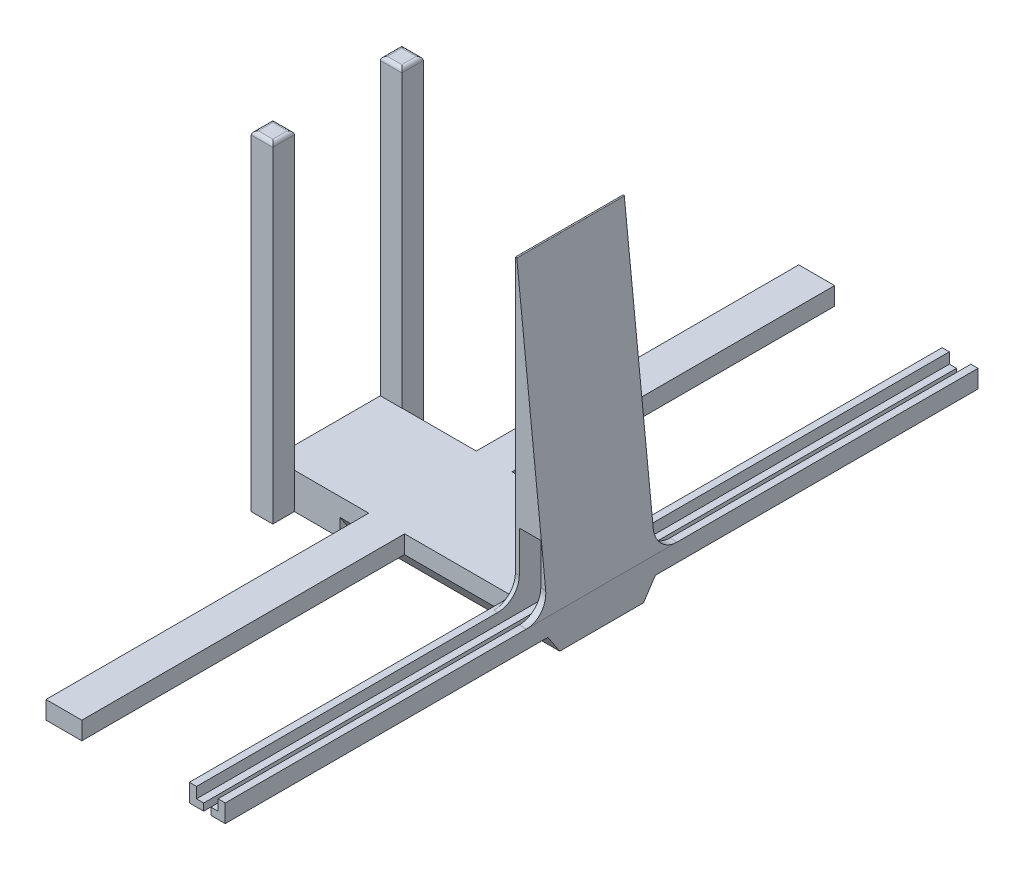
SolidWorks part; units mm, degrees
ref_plane "Front Plane" through (0, 0, 0) normal (0, 0, 1) x (1, 0, 0)
ref_plane "Top Plane" through (0, 0, 0) normal (0, 1, 0) x (1, 0, 0)
ref_plane "Right Plane" through (0, 0, 0) normal (1, 0, 0) x (0, 0, -1)
sketch "Sketch1" plane through (0, -9.4965, 0) normal (0, 1, 0) x (1, 0, 0)
  line L0 (175.5493, -129.0166) -> (125.5493, -129.0166) construction
  line L1 (180.0974, -84.0166) -> (175.0974, -84.0166)
  line L2 (180.0974, -84.0166) -> (180.0974, -189.0166)
  line L3 (180.0974, -189.0166) -> (175.0974, -189.0166)
  line L4 (175.0974, -84.0166) -> (175.0974, -189.0166)
  line L5 (175.5493, -144.0166) -> (125.5493, -144.0166) construction
  dimension "D1" = 60
  dimension "D2" = 60
  dimension "D3" = 5
extrude "Boss-Extrude1" add sketch "Sketch1" along normal blind 5
sketch "Sketch2" plane through (0, -9.4965, 0) normal (0, 0, 1) x (1, 0, 0)
  line L0 (180.0974, 5) -> (175.5493, 48.02)
  line L1 (175.5493, 48.02) -> (175.5493, 5)
  line L2 (180.0974, 5) -> (175.0974, 5) construction
  line L3 (175.5493, 41.5165) -> (175.5493, 56.5165) construction
  line L4 (175.5493, 5) -> (180.0974, 5)
extrude "Boss-Extrude2" add sketch "Sketch2" along normal blind 15 from offset 129
sketch "Sketch3" plane through (0, -9.4965, 0) normal (0, 0, 1) x (1, 0, 0)
  line L1 (175.0974, 5) -> (141.726, 5)
  line L2 (175.0974, 5) -> (175.0974, 0)
  line L3 (175.0974, 0) -> (141.726, 0)
  line L4 (141.726, 5) -> (141.726, 0)
extrude "Boss-Extrude3" add sketch "Sketch3" along normal blind 15 from offset 129
sketch "Sketch4" plane through (0, -9.4965, 0) normal (0, 1, 0) x (1, 0, 0)
  line L0 (175.5493, -144.0166) -> (125.5493, -144.0166) construction
  line L1 (144.726, -147.0166) -> (141.726, -147.0166)
  line L2 (144.726, -147.0166) -> (144.726, -144)
  line L3 (144.726, -144) -> (141.726, -144)
  line L4 (141.726, -147.0166) -> (141.726, -144)
  line L5 (175.5493, -129.0166) -> (125.5493, -129.0166) construction
  line L6 (144.726, -129.0166) -> (141.726, -129.0166)
  line L7 (144.726, -129.0166) -> (144.726, -126.0166)
  line L8 (144.726, -126.0166) -> (141.726, -126.0166)
  line L9 (141.726, -129.0166) -> (141.726, -126.0166)
  dimension "D1" = 3
  dimension "D2" = 3
  dimension "D3" = 3
  dimension "D4" = 3
extrude "Boss-Extrude4" add sketch "Sketch4" along normal blind 46
sketch "Sketch5" plane through (0, 0, 126.0166) normal (0, 0, -1) x (-1, 0, 0)
  circle A0 centre (-143.2664, 42.1424) radius 0.7
fillet "Fillet1" radius 0.5 8 edges at (143.226, 36.5035, 129.0166) (141.726, 36.5035, 127.5166) (143.226, 36.5035, 126.0166) (144.726, 36.5035, 127.5166) (143.226, 36.5035, 147.0166) (141.726, 36.5035, 145.5083) (143.226, 36.5035, 144) (144.726, 36.5035, 145.5083)
fillet "Fillet2" radius 0.1 1 edges at (175.5493, 38.5235, 136.5)
sketch "Sketch6" plane through (177.6366, 18.7798, 0) normal (0.9945, 0.1051, 0) x (0, 0, -1)
  line L0 (-144, -23.4061) -> (-144, 17.9566) construction
  line L1 (-129, -23.4061) -> (-129, 17.9566) construction
  circle A0 centre (-141.5, 22.489) radius 0.7
  circle A1 centre (-131.5, 22.489) radius 0.7
  dimension "D1" = 2.5
  dimension "D2" = 2.5
ref_plane "Plane1" through (180.0974, -4.4965, 144) normal (1, 0, 0) x (0, 0, -1)
fillet "Fillet3" radius 3 2 edges at (177.8233, -4.4965, 129) (177.8233, -4.4965, 144)
pattern_linear "LPattern2" count 2 spacing 20 along (-1, 0, 0) of "Boss-Extrude1"
sketch "Sketch7" plane through (180.0974, 0, 0) normal (1, 0, 0) x (0, 0, -1)
  line L0 (-189.0166, -9.4965) -> (-84.0166, -9.4965)
  line L1 (-84.0166, -9.4965) -> (-84.0166, -6.9965)
  line L2 (-84.0166, -4.4965) -> (-84.0166, -9.4965) construction
  line L3 (-84.0166, -6.9965) -> (-129.0166, -6.9965)
  line L4 (-129.0166, -6.9965) -> (-130.6749, -9.4965)
  line L5 (-130.6749, -9.4965) -> (-142.3583, -9.4965)
  line L6 (-142.3583, -9.4965) -> (-144.0166, -6.9965)
  line L7 (-144.0166, -6.9965) -> (-189.0166, -6.9965)
  line L8 (-189.0166, -4.4965) -> (-189.0166, -9.4965) construction
  line L9 (-189.0166, -6.9965) -> (-189.0166, -9.4965)
  line M7 (-189.0166, -9.4965) -> (-84.0166, -9.4965)
  line M8 (-84.0166, -9.4965) -> (-84.0166, -4.4965)
  line M12 (-189.0166, -4.4965) -> (-189.0166, -9.4965)
  dimension "D1" = 2.5
  dimension "D2" = 45
  dimension "D3" = 45
  dimension "D4" = 2.5
  dimension "D5" = 3
  dimension "D6" = 3
extrude "Cut-Extrude3" cut sketch "Sketch7" against normal blind 29 contours L3 L4 L0 M8 | L6 L7 M12 M7 region at (180.0974, -8.2541, 166.0996) region at (180.0974, -8.2541, 106.9337)
sketch "Sketch10" plane through (0, -4.4965, 0) normal (0, 1, 0) x (1, 0, 0)
  line L1 (240.0974, -85.051) -> (151.0974, -85.051)
  line L2 (240.0974, -85.051) -> (240.0974, -92.051)
  line L3 (240.0974, -92.051) -> (151.0974, -92.051)
  line L4 (151.0974, -85.051) -> (151.0974, -92.051)
sketch "Sketch11" plane through (0, 0, 84.0166) normal (0, 0, -1) x (-1, 0, 0)
  line L0 (-178.0974, -6.9965) -> (-178.0974, -5.9965)
  line L1 (-175.0974, -6.9965) -> (-180.0974, -6.9965) construction
  line L2 (-178.0974, -5.9965) -> (-179.0974, -5.9965)
  line L3 (-179.0974, -5.9965) -> (-179.0974, 4.2082)
  line L4 (-179.0974, 4.2082) -> (-176.0974, 4.2082)
  line L5 (-176.0974, 4.2082) -> (-176.0974, -5.9965)
  line L6 (-176.0974, -5.9965) -> (-177.0974, -5.9965)
  line L7 (-177.0974, -5.9965) -> (-177.0974, -6.9965)
  line L8 (-177.0974, -6.9965) -> (-178.0974, -6.9965)
  line L9 (-180.0974, -4.4965) -> (-180.0974, -6.9965) construction
  line L10 (-175.0974, -4.4965) -> (-175.0974, -6.9965) construction
  dimension "D1" = 2
  dimension "D2" = 2
  dimension "D3" = 1
  dimension "D4" = 1
  dimension "D5" = 1
  dimension "D6" = 1
extrude "Cut-Extrude4" cut sketch "Sketch11" against normal blind 106
